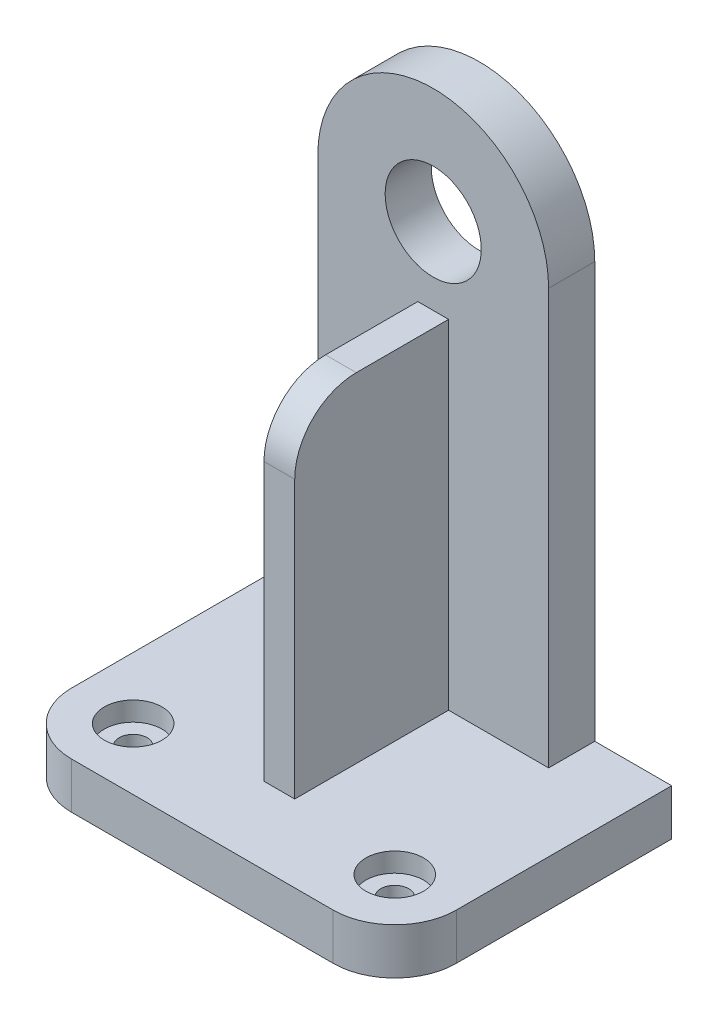
SolidWorks part; units mm, degrees
note: The reader was unsure of these and kept them because the rebuilt part matched: shared geometry of "草图1<3>".
ref_plane "前视基准面" through (0, 0, 0) normal (0, 0, 1) x (1, 0, 0)
ref_plane "上视基准面" through (0, 0, 0) normal (0, 1, 0) x (1, 0, 0)
ref_plane "右视基准面" through (0, 0, 0) normal (1, 0, 0) x (0, 0, -1)
other "Configuration Table"
sketch "草图1" plane through (0, 0, 0) normal (0, 1, 0) x (1, 0, 0)
  line L1 (-50, 36) -> (50, 36)
  line L2 (-50, 36) -> (-50, -20)
  line L3 (-34, -36) -> (34, -36)
  line L4 (50, 36) -> (50, -20)
  line L5 (-50, 36) -> (50, -36) construction
  line L6 (-50, -36) -> (50, 36) construction
  arc A0 (34, -36) -> (50, -20) centre (34, -20) ccw
  arc A1 (-50, -20) -> (-34, -36) centre (-34, -20) ccw
  circle A2 centre (-34, -20) radius 7.5
  circle A3 centre (-34, -20) radius 3.6357
  circle A4 centre (34, -20) radius 7.5
  circle A5 centre (34, -20) radius 3.6357
  point P0 (0, 0)
  dimension "D3" = 16
  dimension "D4" = 15
  dimension "D5" = 7.2713
  dimension "D1" = 100
  dimension "D2" = 72
extrude "凸台-拉伸1" add sketch "草图1" along normal blind 12 contours L2 A1 L3 A0 L4 L1
extrude "切除-拉伸1" cut sketch "草图1<3>" along normal blind 12 contours A5 | A3
sketch "草图1<3>" plane through (0, 0, 0) normal (0, 1, 0) x (1, 0, 0) same geometry as "草图1"
sketch "草图2" plane through (0, 12, 0) normal (0, 1, 0) x (1, 0, 0)
  line L4 (50, 36) -> (-50, 36)
  line L5 (50, -20) -> (50, 36)
  line L6 (-34, -36) -> (34, -36)
  line L7 (-50, 36) -> (-50, -20)
  line L8 (50, 36) -> (-50, 36)
  line L9 (50, -20) -> (50, 36)
  line L10 (-34, -36) -> (34, -36)
  line L11 (-50, 36) -> (-50, -20)
  circle A1 centre (34, -20) radius 3.6357
  circle A2 centre (34, -20) radius 3.6357
  circle A3 centre (34, -20) radius 7.5
  circle A4 centre (34, -20) radius 7.5
  circle A5 centre (-34, -20) radius 3.6357
  circle A6 centre (-34, -20) radius 3.6357
  circle A7 centre (-34, -20) radius 7.5
  circle A8 centre (-34, -20) radius 7.5
  arc A10 (34, -36) -> (50, -20) centre (34, -20) ccw
  arc A11 (-50, -20) -> (-34, -36) centre (-34, -20) ccw
  arc A12 (34, -36) -> (50, -20) centre (34, -20) ccw
  arc A13 (-50, -20) -> (-34, -36) centre (-34, -20) ccw
  dimension "D1" = 0
  dimension "D2" = 0
  dimension "D3" = 0
  dimension "D4" = 0
  dimension "D5" = 0
extrude "切除-拉伸2" cut sketch "草图2" against normal blind 5 contours A8 | A4
sketch "草图4" plane through (0, 0, -36) normal (0, 0, -1) x (-1, 0, 0)
  line L0 (0, 12) -> (-30, 12)
  line L1 (50, 12) -> (-50, 12) construction
  line L2 (0, 12) -> (30, 12)
  line L3 (0, 12) -> (0, 57.4222) construction
  line L5 (50, 0) -> (-50, 0) construction
  line L6 (-30, 12) -> (-30, 120)
  line L8 (30, 120) -> (30, 12)
  circle A0 centre (0, 120) radius 12.5
  circle A1 centre (0, 120) radius 30
  dimension "D3" = 60
  dimension "D4" = 25
  dimension "D1" = 30
  dimension "D2" = 30
  dimension "D5" = 120
extrude "凸台-拉伸2" add sketch "草图4" against normal blind 12
sketch "草图5" plane through (0, 0, 0) normal (1, 0, 0) x (0, 0, -1)
  line L0 (24, 12) -> (-16, 12)
  line L1 (36, 12) -> (-20, 12) construction
  line L2 (-16, 12) -> (-16, 100)
  line L3 (-16, 100) -> (24, 100)
  line L4 (24, 12) -> (24, 120) construction
  line L5 (24, 100) -> (24, 12)
  dimension "D1" = 88
  dimension "D2" = 40
extrude "凸台-拉伸3" add sketch "草图5" along normal mid plane 8
fillet "圆角1" radius 16 1 edges at (0, 100, 16)
